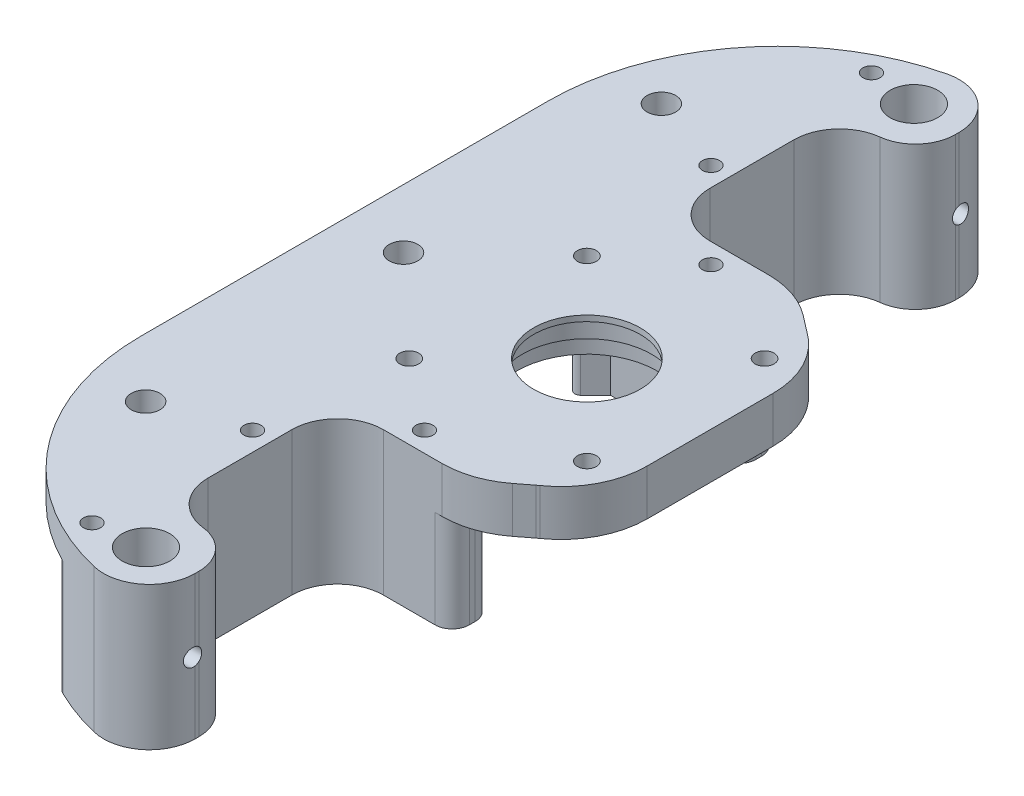
SolidWorks part; units mm, degrees
material "ABS"
ref_plane "Płaszczyzna przednia" through (0, 0, 0) normal (0, 0, 1) x (1, 0, 0)
ref_plane "Płaszczyzna górna" through (0, 0, 0) normal (0, 1, 0) x (1, 0, 0)
ref_plane "Płaszczyzna prawa" through (0, 0, 0) normal (1, 0, 0) x (0, 0, -1)
sketch "Szkic2" plane through (0, 0, 0) normal (0, 1, 0) x (1, 0, 0)
  line L0 (-29.6604, 52.1749) -> (-33.4767, 55.9912) construction
  line L1 (-33.4767, 55.9912) -> (-67.8442, 55.9912) construction
  line L2 (-67.8442, 55.9912) -> (-71.6604, 52.1749) construction
  line L3 (-71.6604, 52.1749) -> (-71.6604, 17.8074) construction
  line L4 (-71.6604, 17.8074) -> (-67.8442, 13.9912) construction
  line L5 (-67.8442, 13.9912) -> (-33.4767, 13.9912) construction
  line L6 (-33.4767, 13.9912) -> (-29.6604, 17.8074) construction
  line L7 (-29.6604, 17.8074) -> (-29.6604, 52.1749) construction
  line L8 (-50.6604, 34.9912) -> (-92.6604, 34.9912) construction
  line L9 (-72.3604, -11.5088) -> (-92.9604, -11.5088) construction
  line L10 (-65.6604, 13.4912) -> (-33.2696, 13.4912)
  line L11 (-33.2696, 13.4912) -> (-29.1604, 17.6003) construction
  line L12 (-29.1604, 17.6003) -> (-29.1604, 52.382)
  line L13 (-29.1604, 52.382) -> (-33.2696, 56.4912) construction
  line L14 (-33.2696, 56.4912) -> (-65.6604, 56.4912)
  line L15 (-65.6604, 81.4912) -> (-33.2696, 56.4912)
  line L16 (-72.3604, 17.8003) -> (-72.3604, -11.5088)
  line L17 (-92.9604, -11.5088) -> (-92.9604, 81.4912)
  line L18 (-69.0104, 109.9912) -> (-69.0104, 102.9912) construction
  line L19 (-65.6604, -11.5088) -> (-65.6604, 13.4912)
  line L20 (-65.6604, -11.5088) -> (-33.2696, 13.4912)
  line L21 (-33.2696, 13.4912) -> (-29.1604, 13.4912)
  line L22 (-29.1604, 13.4912) -> (-29.1604, 17.6003)
  line L23 (-29.1604, 52.382) -> (-29.1604, 56.4912)
  line L24 (-29.1604, 56.4912) -> (-33.2696, 56.4912)
  line L25 (-68.0513, 13.4912) -> (-72.3604, 17.8003)
  line L26 (-68.0513, 56.4912) -> (-72.3604, 52.182)
  line L27 (-65.6604, 81.4912) -> (-65.6604, 56.4912)
  line L28 (-92.9604, 81.4912) -> (-92.9604, 109.9912)
  line L29 (-72.3604, 52.182) -> (-72.3604, 81.4912)
  line L30 (-72.3604, 81.4912) -> (-92.9604, 81.4912) construction
  line L31 (-65.6604, 13.4912) -> (-68.0513, 13.4912)
  line L32 (-68.0513, 56.4912) -> (-65.6604, 56.4912)
  line L33 (-82.6604, -11.5088) -> (-82.6604, 81.4912) construction
  line L34 (-65.6604, 13.4912) -> (-65.6604, 6.4912)
  line L35 (-65.6604, 6.4912) -> (-45.6604, 6.4912)
  line L36 (-45.6604, 6.4912) -> (-45.6604, 13.4912)
  line L37 (-45.6604, 13.4912) -> (-65.6604, 13.4912)
  line L38 (-65.6604, 63.4912) -> (-45.6604, 63.4912)
  line L39 (-45.6604, 63.4912) -> (-45.6604, 56.4912)
  line L40 (-65.6604, 56.4912) -> (-65.6604, 63.4912)
  line L41 (-45.6604, 56.4912) -> (-65.6604, 56.4912)
  line L42 (-92.9604, 109.9912) -> (-72.3604, 109.9912)
  line L43 (-92.9604, -11.5088) -> (-92.9604, -40.0088)
  line L44 (-65.6604, 81.4912) -> (-65.6604, 109.9912)
  line L45 (-69.0104, -40.0088) -> (-69.0104, 109.9912) construction
  line L46 (-45.6604, 9.9912) -> (-72.3604, 9.9912) construction
  line L47 (-45.6604, 59.9912) -> (-72.3604, 59.9912) construction
  line L48 (-72.3604, 109.9912) -> (-52.3604, 109.9912)
  line L49 (-52.3604, -40.0088) -> (-52.3604, 13.4912)
  line L50 (-72.3604, -40.0088) -> (-52.3604, -40.0088)
  line L51 (-72.3604, 109.9912) -> (-72.3604, -40.0088)
  line L52 (-65.6604, 109.9912) -> (-72.3604, 109.9912)
  line L53 (-72.3604, -11.5088) -> (-72.3604, -40.0088)
  line L54 (-65.6604, -40.0088) -> (-65.6604, -11.5088)
  line L55 (-92.9604, -40.0088) -> (-72.3604, -40.0088)
  line L56 (-52.3604, 56.4912) -> (-52.3604, 109.9912)
  circle A0 centre (-50.6604, 34.9912) radius 11.75 construction
  circle A1 centre (-66.1604, 50.4912) radius 1.5 construction
  circle A2 centre (-35.1604, 50.4912) radius 1.5 construction
  circle A3 centre (-35.1604, 19.4912) radius 1.5 construction
  circle A4 centre (-66.1604, 19.4912) radius 1.5 construction
  circle A5 centre (-50.6604, 34.9912) radius 4 construction
  circle A6 centre (-50.6604, 34.9912) radius 11 construction
  circle A7 centre (-82.6604, 34.9912) radius 2.5
  circle A8 centre (-82.6604, -10.0088) radius 2.5
  circle A9 centre (-82.6604, 79.9912) radius 2.5
  circle A10 centre (-50.6604, 34.9912) radius 12.25 construction
  circle A11 centre (-66.1604, 19.4912) radius 1.65
  circle A12 centre (-66.1604, 50.4912) radius 1.65
  circle A13 centre (-35.1604, 50.4912) radius 1.65
  circle A14 centre (-35.1604, 19.4912) radius 1.65
  circle A15 centre (-69.0104, 9.9912) radius 1.5 construction
  circle A16 centre (-69.0104, 102.9912) radius 1.5
  circle A17 centre (-69.0104, -33.0088) radius 1.5
  circle A23 centre (-54.0104, 9.9912) radius 1.5
  circle A24 centre (-69.0104, -5.0088) radius 1.5
  circle A25 centre (-54.0104, 59.9912) radius 1.5
  circle A26 centre (-69.0104, 74.9912) radius 1.5
  circle A27 centre (-69.0104, 59.9912) radius 1.5 construction
  circle A28 centre (-50.6604, 34.9912) radius 11.3
  circle A29 centre (-60.5945, -32.0088) radius 4.15
  circle A30 centre (-60.5945, 101.9912) radius 4.15
  point P40 (-92.9604, 34.9912)
  point P66 (-92.9604, 34.9912)
  dimension "D1" = 45
  dimension "D2" = 7
extrude "Dodanie-wyciągnięcie1" add sketch "Szkic2" along normal blind 5 contours L26 L51 L25 L31 L10 L37 L21 L22 L12 L23 L24 L14 L41 L32 A28 A14 A13 A12 A11 | L43 L55 L51 L16 L29 L42 L28 L17 A8 A9 | L50 L54 L19 L31 L25 L16 L51 A24 | L35 L49 L10 L19 A23 | L49 L35 L36 L37 | L20 L49 L35 L19 | L54 L50 L49 L20 A29 | L49 L20 L10 L36 L35 | L48 L51 L29 L26 L32 L27 L44 A16 A26 | L38 L56 L15 L27 | L15 L56 L48 L44 A30 | L41 L56 L38 L27 A25 | L56 L14 L39 L38 | L56 L38 L39 L14 L15 region at (-66.8559, 0, -14.1007) region at (-59.4213, 0, -9.9912) region at (-69.0607, 0, 12.2889) region at (-49.0104, 0, -9.9912) region at (-59.8946, 0, 0.2837) region at (-44.4892, 0, -7.8734) region at (-58.4076, 0, 21.8309) region at (-73.8745, 0, -3.1457) region at (-69.0607, 0, -82.2712) region at (-59.4213, 0, -59.9912) region at (-49.0104, 0, -59.9912) region at (-59.8946, 0, -70.2661) region at (-58.4076, 0, -91.8132) region at (-44.4892, 0, -62.1089)
extrude "Dodanie-wyciągnięcie2" add sketch "Szkic2<3>" against normal blind 20 contours L49 L35 L36 L37 | L35 L49 L10 L19 A23 | L50 L54 L19 L31 L25 L16 L51 A24 | L48 L51 L29 L26 L32 L27 L44 A16 A26 | L41 L56 L38 L27 A25 | L56 L14 L39 L38 region at (-59.4213, 0, -9.9912) region at (-69.0607, 0, 12.2889) region at (-49.0104, 0, -9.9912) region at (-69.0607, 0, -82.2712) region at (-59.4213, 0, -59.9912) region at (-49.0104, 0, -59.9912)
sketch "Szkic2<3>" plane through (0, 0, 0) normal (0, 1, 0) x (1, 0, 0) same geometry as "Szkic2"
fillet "Zaokrąglenie1" radius 7 2 edges at (-52.3604, 2.5, -109.9912) (-52.3604, 2.5, 40.0088)
sketch "Szkic3" plane through (0, 0, 0) normal (0, -1, 0) x (1, 0, 0)
  line L0 (-65.6604, -109.9912) -> (-59.3604, -109.9912) construction
  line L1 (-65.6604, 40.0088) -> (-59.3604, 40.0088) construction
  line L2 (-65.6604, -109.9912) -> (-59.3604, -109.9912)
  line L3 (-65.6604, 40.0088) -> (-59.3604, 40.0088)
  line L4 (-65.6604, 24.0088) -> (-59.3604, 24.0088)
  line L5 (-56.4445, 32.0088) -> (-64.7445, 32.0088) construction
  line L6 (-56.4445, -101.9912) -> (-64.7445, -101.9912) construction
  line L7 (-65.6604, -93.9912) -> (-59.3604, -93.9912)
  line L8 (-52.3604, 33.0088) -> (-52.3604, 31.0088)
  line L9 (-65.6604, 40.0088) -> (-65.6604, 24.0088)
  line L10 (-52.3604, -100.9912) -> (-52.3604, -102.9912)
  line L11 (-65.6604, -93.9912) -> (-65.6604, -109.9912)
  arc A0 (-59.3604, -109.9912) -> (-52.3604, -102.9912) centre (-59.3604, -102.9912) ccw construction
  arc A1 (-52.3604, 33.0088) -> (-59.3604, 40.0088) centre (-59.3604, 33.0088) ccw construction
  arc A2 (-59.3604, -109.9912) -> (-52.3604, -102.9912) centre (-59.3604, -102.9912) ccw
  arc A3 (-52.3604, 33.0088) -> (-59.3604, 40.0088) centre (-59.3604, 33.0088) ccw
  circle A4 centre (-60.5945, 32.0088) radius 4.15 construction
  circle A5 centre (-60.5945, -101.9912) radius 4.15 construction
  arc A6 (-52.3604, 31.0088) -> (-59.3604, 24.0088) centre (-59.3604, 31.0088) cw
  arc A7 (-59.3604, -93.9912) -> (-52.3604, -100.9912) centre (-59.3604, -100.9912) cw
  circle A8 centre (-60.5945, 32.0088) radius 4.15
  circle A9 centre (-60.5945, -101.9912) radius 4.15
extrude "Dodanie-wyciągnięcie3" add sketch "Szkic3" along normal up to surface (20 mm away) up to face at (-62.202, -20, 3.1789)
fillet "Zaokrąglenie2" radius 3 4 edges at (-45.6604, -10, -63.4912) (-45.6604, -10, -56.4912) (-45.6604, -10, -13.4912) (-45.6604, -10, -6.4912)
fillet "Zaokrąglenie3" radius 10 2 edges at (-33.2696, 2.5, -56.4912) (-33.2696, 2.5, -13.4912)
sketch "Szkic4" plane through (0, 0, 0) normal (0, -1, 0) x (1, 0, 0)
  line L1 (-52.3604, 31.0088) -> (-52.3604, 1.2436) construction
  line L4 (-65.6604, -6.4912) -> (-48.6604, -6.4912) construction
  line L5 (-52.3604, 31.0088) -> (-52.3604, 1.2436)
  line L6 (-65.6604, 24.0088) -> (-65.6604, -6.4912) construction
  line L7 (-65.6604, 24.0088) -> (-59.3604, 24.0088) construction
  line L8 (-52.3604, -71.2259) -> (-52.3604, -100.9912) construction
  line L9 (-59.3604, -93.9912) -> (-65.6604, -93.9912) construction
  line L12 (-52.3604, -71.2259) -> (-52.3604, -100.9912)
  line L13 (-59.3604, -93.9912) -> (-65.6604, -93.9912)
  line L14 (-65.6604, -63.4912) -> (-48.6604, -63.4912) construction
  line L15 (-65.6604, -93.9912) -> (-65.6604, -63.4912) construction
  line L16 (-48.6604, -63.4912) -> (-42.339, -63.4912)
  line L17 (-52.3604, -71.2259) -> (-35.9693, -58.5749) construction
  line L18 (-42.339, -63.4912) -> (-52.3604, -71.2259)
  line L19 (-48.6604, -6.4912) -> (-42.339, -6.4912)
  line L20 (-52.3604, 1.2436) -> (-35.9693, -11.4075) construction
  line L21 (-42.339, -6.4912) -> (-52.3604, 1.2436)
  line L22 (-65.6604, -93.9912) -> (-65.6604, -63.4912)
  line L23 (-65.6604, -63.4912) -> (-48.6604, -63.4912)
  line L24 (-65.6604, 24.0088) -> (-59.3604, 24.0088)
  line L25 (-65.6604, 24.0088) -> (-65.6604, -6.4912)
  line L26 (-65.6604, -6.4912) -> (-48.6604, -6.4912)
  arc A2 (-59.3604, 24.0088) -> (-52.3604, 31.0088) centre (-59.3604, 31.0088) ccw construction
  arc A5 (-59.3604, 24.0088) -> (-52.3604, 31.0088) centre (-59.3604, 31.0088) ccw
  arc A6 (-52.3604, -100.9912) -> (-59.3604, -93.9912) centre (-59.3604, -100.9912) ccw construction
  arc A9 (-52.3604, -100.9912) -> (-59.3604, -93.9912) centre (-59.3604, -100.9912) ccw
extrude "Wytnij-wyciągnięcie1" cut sketch "Szkic4" against normal through all
fillet "Zaokrąglenie4" radius 15 4 edges at (-29.1604, 2.5, -56.4912) (-29.1604, 2.5, -13.4912) (-42.339, 2.5, -63.4912) (-42.339, 2.5, -6.4912)
fillet "Zaokrąglenie5" radius 1 2 edges at (-72.3604, -10, -52.182) (-72.3604, -10, -17.8003)
fillet "Zaokrąglenie6" radius 40 2 edges at (-92.9604, 2.5, -109.9912) (-92.9604, 2.5, 40.0088)
fillet "Zaokrąglenie7" radius 3 2 edges at (-72.3604, -10, -105.4871) (-72.3604, -10, 35.5047)
fillet "Zaokrąglenie10" radius 8 2 edges at (-59.3604, -7.5, -109.9912) (-59.3604, -7.5, 40.0088)
fillet "Zaokrąglenie11" radius 8 4 edges at (-65.6604, -7.5, 24.0088) (-65.6604, -7.5, -93.9912) (-65.6604, -7.5, -63.4912) (-65.6604, -7.5, -6.4912)
sketch "Szkic6" plane through (0, 5, 0) normal (0, 1, 0) x (1, 0, 0)
  circle A0 centre (-50.6604, 34.9912) radius 11.3 construction
  circle A1 centre (-50.6604, 34.9912) radius 11.3
  circle A2 centre (-50.6604, 34.9912) radius 9.3
  dimension "D1" = 2
extrude "Dodanie-wyciągnięcie4" add sketch "Szkic6" against normal blind 1
sketch "Szkic7" plane through (0, 0, 0) normal (0, -1, 0) x (1, 0, 0)
  line L0 (-72.3604, -15.3861) -> (-72.3604, -54.5963)
  line L14 (-92.9604, 0.5241) -> (-92.9604, -70.5065)
  line L15 (-72.3604, -103.6733) -> (-72.3604, -54.5963)
  line L16 (-70.6533, -53.8892) -> (-68.0513, -56.4912)
  line L17 (-68.0513, -56.4912) -> (-48.6604, -56.4912)
  line L18 (-45.6604, -59.4912) -> (-45.6604, -60.4912)
  line L19 (-48.6604, -63.4912) -> (-47.4545, -63.4912)
  line L20 (-38.2895, -60.3656) -> (-35.9693, -58.5749)
  line L21 (-29.1604, -45.9856) -> (-29.1604, -23.9967)
  line L22 (-35.9693, -11.4075) -> (-38.2895, -9.6167)
  line L23 (-47.4545, -6.4912) -> (-48.6604, -6.4912)
  line L24 (-45.6604, -9.4912) -> (-45.6604, -10.4912)
  line L25 (-48.6604, -13.4912) -> (-68.0513, -13.4912)
  line L26 (-68.0513, -13.4912) -> (-70.6533, -16.0932)
  line L27 (-72.3604, -15.3861) -> (-72.3604, 33.691)
  line L30 (-70.6533, -53.8892) -> (-68.0513, -56.4912)
  line L31 (-68.0513, -56.4912) -> (-48.6604, -56.4912)
  line L32 (-45.6604, -59.4912) -> (-45.6604, -60.4912)
  line L33 (-48.6604, -63.4912) -> (-47.4545, -63.4912)
  line L34 (-38.2895, -60.3656) -> (-35.9693, -58.5749)
  line L35 (-29.1604, -45.9856) -> (-29.1604, -23.9967)
  line L36 (-35.9693, -11.4075) -> (-38.2895, -9.6167)
  line L37 (-47.4545, -6.4912) -> (-48.6604, -6.4912)
  line L38 (-45.6604, -9.4912) -> (-45.6604, -10.4912)
  line L39 (-48.6604, -13.4912) -> (-68.0513, -13.4912)
  line L40 (-68.0513, -13.4912) -> (-70.6533, -16.0932)
  circle A0 centre (-50.6604, -34.9912) radius 12.25
  circle A1 centre (-66.1604, -19.4912) radius 1.65 construction
  circle A2 centre (-66.1604, -50.4912) radius 1.65 construction
  circle A3 centre (-35.1604, -50.4912) radius 1.65 construction
  circle A4 centre (-35.1604, -19.4912) radius 1.65 construction
  circle A5 centre (-66.1604, -19.4912) radius 1.65
  circle A6 centre (-66.1604, -50.4912) radius 1.65
  circle A7 centre (-35.1604, -50.4912) radius 1.65
  circle A8 centre (-35.1604, -19.4912) radius 1.65
  arc A25 (-92.9604, -70.5065) -> (-70.6902, -106.3625) centre (-52.9604, -70.5065) ccw
  arc A26 (-72.3604, -103.6733) -> (-70.6902, -106.3625) centre (-69.3604, -103.6733) ccw
  arc A27 (-70.6533, -53.8892) -> (-72.3604, -54.5963) centre (-71.3604, -54.5963) ccw
  arc A28 (-45.6604, -59.4912) -> (-48.6604, -56.4912) centre (-48.6604, -59.4912) ccw
  arc A29 (-48.6604, -63.4912) -> (-45.6604, -60.4912) centre (-48.6604, -60.4912) ccw
  arc A30 (-47.4545, -63.4912) -> (-38.2895, -60.3656) centre (-47.4545, -48.4912) ccw
  arc A31 (-35.5797, -58.289) -> (-35.9693, -58.5749) centre (-29.8593, -66.4912) ccw
  arc A32 (-35.5797, -58.289) -> (-29.1604, -45.9856) centre (-44.1604, -45.9856) ccw
  arc A33 (-29.1604, -23.9967) -> (-35.5797, -11.6934) centre (-44.1604, -23.9967) ccw
  arc A34 (-35.9693, -11.4075) -> (-35.5797, -11.6934) centre (-29.8593, -3.4912) ccw
  arc A35 (-38.2895, -9.6167) -> (-47.4545, -6.4912) centre (-47.4545, -21.4912) ccw
  arc A36 (-45.6604, -9.4912) -> (-48.6604, -6.4912) centre (-48.6604, -9.4912) ccw
  arc A37 (-48.6604, -13.4912) -> (-45.6604, -10.4912) centre (-48.6604, -10.4912) ccw
  arc A38 (-72.3604, -15.3861) -> (-70.6533, -16.0932) centre (-71.3604, -15.3861) ccw
  arc A39 (-70.6902, 36.3802) -> (-72.3604, 33.691) centre (-69.3604, 33.691) ccw
  arc A40 (-70.6902, 36.3802) -> (-92.9604, 0.5241) centre (-52.9604, 0.5241) ccw
  arc A43 (-70.6533, -53.8892) -> (-72.3604, -54.5963) centre (-71.3604, -54.5963) ccw
  arc A44 (-45.6604, -59.4912) -> (-48.6604, -56.4912) centre (-48.6604, -59.4912) ccw
  arc A45 (-48.6604, -63.4912) -> (-45.6604, -60.4912) centre (-48.6604, -60.4912) ccw
  arc A46 (-47.4545, -63.4912) -> (-38.2895, -60.3656) centre (-47.4545, -48.4912) ccw
  arc A47 (-35.5797, -58.289) -> (-35.9693, -58.5749) centre (-29.8593, -66.4912) ccw
  arc A48 (-35.5797, -58.289) -> (-29.1604, -45.9856) centre (-44.1604, -45.9856) ccw
  arc A49 (-29.1604, -23.9967) -> (-35.5797, -11.6934) centre (-44.1604, -23.9967) ccw
  arc A50 (-35.9693, -11.4075) -> (-35.5797, -11.6934) centre (-29.8593, -3.4912) ccw
  arc A51 (-38.2895, -9.6167) -> (-47.4545, -6.4912) centre (-47.4545, -21.4912) ccw
  arc A52 (-45.6604, -9.4912) -> (-48.6604, -6.4912) centre (-48.6604, -9.4912) ccw
  arc A53 (-48.6604, -13.4912) -> (-45.6604, -10.4912) centre (-48.6604, -10.4912) ccw
  arc A54 (-72.3604, -15.3861) -> (-70.6533, -16.0932) centre (-71.3604, -15.3861) ccw
  dimension "D1" = 0
extrude "Dodanie-wyciągnięcie5" add sketch "Szkic7" along normal blind 3
sketch "Szkic9" plane through (-52.3604, 0, 0) normal (1, 0, 0) x (0, 0, -1)
  line L0 (-36.1588, -20) -> (-27.8588, -20) construction
  line L1 (-36.1588, -20) -> (-27.8588, -20) construction
  line L2 (-27.8588, 5) -> (-36.1588, 5) construction
  line L3 (-27.8588, 5) -> (-36.1588, 5) construction
  line L4 (97.8412, -20) -> (106.1412, -20) construction
  line L5 (106.1412, 5) -> (97.8412, 5) construction
  line L6 (97.8412, -20) -> (106.1412, -20) construction
  line L7 (106.1412, 5) -> (97.8412, 5) construction
  line L8 (101.9912, 5) -> (101.9912, -20) construction
  line L9 (-32.0088, 5) -> (-32.0088, -20) construction
  circle A0 centre (-32.0088, -7.5) radius 1.5
  circle A1 centre (101.9912, -7.5) radius 1.5
extrude "Wytnij-wyciągnięcie4" cut sketch "Szkic9" against normal up to surface (4.3646 mm away) contours A0 up to face at (-60.5945, 5, 36.1588)
extrude "Wytnij-wyciągnięcie5" cut sketch "Szkic9<3>" against normal up to surface (4.3646 mm away) contours A1 up to face at (-60.5945, 5, -97.8412)
sketch "Szkic9<3>" plane through (-52.3604, 0, 0) normal (1, 0, 0) x (0, 0, -1) same geometry as "Szkic9"
